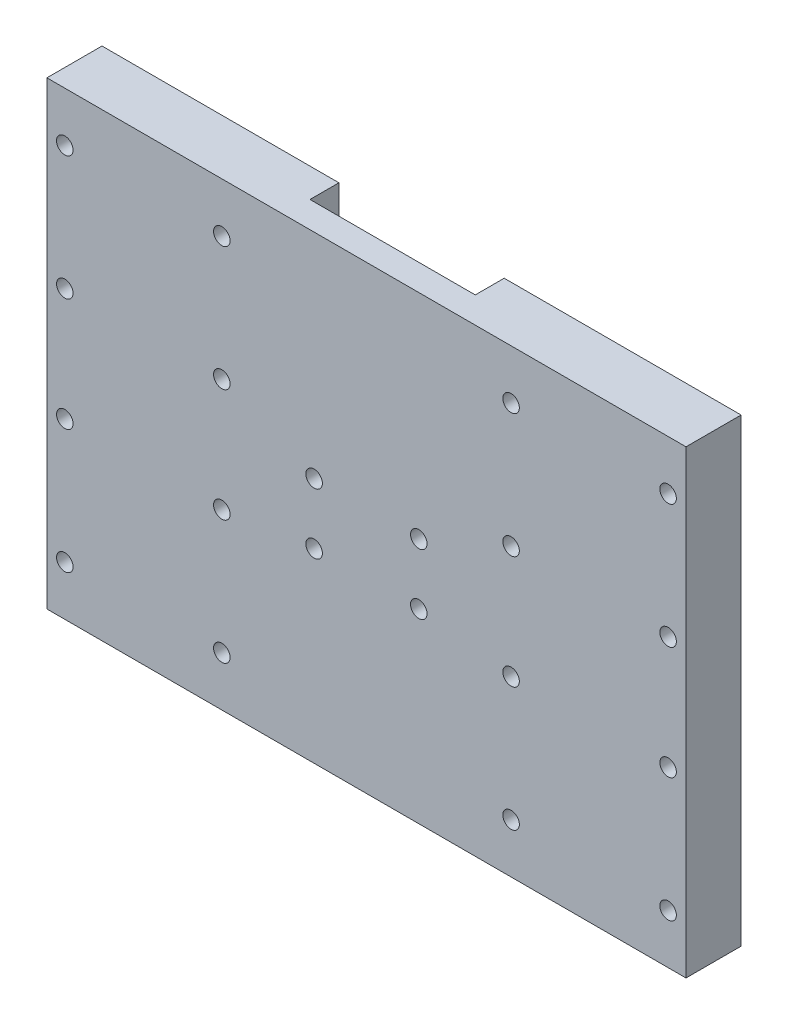
SolidWorks part; units mm, degrees
ref_plane "Piano frontale" through (0, 0, 0) normal (0, 0, 1) x (1, 0, 0)
ref_plane "Piano superiore" through (0, 0, 0) normal (0, 1, 0) x (1, 0, 0)
ref_plane "Piano destro" through (0, 0, 0) normal (1, 0, 0) x (0, 0, -1)
sketch "Schizzo1" plane through (0, 0, 0) normal (0, 0, 1) x (1, 0, 0)
  line L1 (116, -83.5) -> (-116, -83.5)
  line L2 (116, -83.5) -> (116, 83.5)
  line L3 (116, 83.5) -> (-116, 83.5)
  line L4 (-116, -83.5) -> (-116, 83.5)
  line L5 (116, -83.5) -> (-116, 83.5) construction
  line L6 (116, 83.5) -> (-116, -83.5) construction
  point P0 (0, 0)
  dimension "D1" = 232
  dimension "D2" = 167
extrude "Estrusione-Estrusione1" add sketch "Schizzo1" along normal blind 20
sketch "Schizzo3" plane through (0, 0, 20) normal (0, 0, 1) x (1, 0, 0)
  circle A8 centre (19, 6) radius 3
  circle A9 centre (-19, 6) radius 3
  circle A10 centre (-19, -16) radius 3
  circle A11 centre (19, -16) radius 3
  circle A14 centre (-109.5, 65.5) radius 3
  circle A15 centre (-52.5, 65.5) radius 3
  circle A18 centre (-109.5, 20.5) radius 3
  circle A19 centre (-52.5, 20.5) radius 3
  circle A24 centre (-109.5, -65.5) radius 3
  circle A25 centre (-109.5, -20.5) radius 3
  circle A26 centre (-52.5, -65.5) radius 3
  circle A27 centre (-52.5, -20.5) radius 3
extrude "Taglio-Estrusione1" cut sketch "Schizzo3" against normal through all
sketch "Schizzo4" plane through (0, 83.5, 0) normal (0, 1, 0) x (1, 0, 0)
  line L0 (116, 0) -> (-116, 0) construction
  line L1 (30, 0) -> (-30, 0)
  line L2 (30, 0) -> (30, -10.5)
  line L3 (30, -10.5) -> (-30, -10.5)
  line L4 (-30, 0) -> (-30, -10.5)
  dimension "D1" = 10.5
extrude "Taglio-Estrusione2" cut sketch "Schizzo4" against normal through all
mirror "Specchia1" about plane through (0, 0, 0) normal (1, 0, 0) of "Taglio-Estrusione1"
